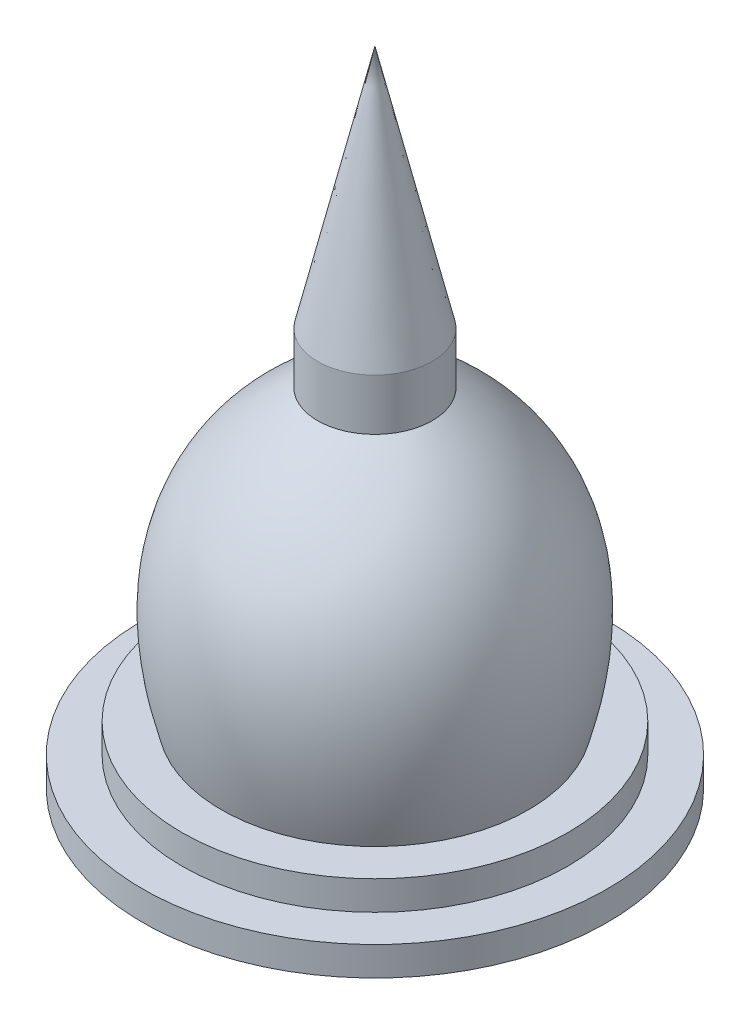
SolidWorks part; units mm, degrees
ref_plane "Front Plane" through (0, 0, 0) normal (0, 0, 1) x (1, 0, 0)
ref_plane "Top Plane" through (0, 0, 0) normal (0, 1, 0) x (1, 0, 0)
ref_plane "Right Plane" through (0, 0, 0) normal (1, 0, 0) x (0, 0, -1)
sketch "Sketch1" plane through (0, 0, 0) normal (0, 0, 1) x (1, 0, 0)
  line L0 (0, 0) -> (0, 120.0387) construction
  line L1 (0, 0) -> (-60, 0)
  line L2 (-60, 0) -> (-60, 7.5011)
  line L3 (-49.8183, 15.0034) -> (-39.6365, 15.0034)
  line L4 (-14.8078, 89.5954) -> (-14.8078, 102.8571)
  line L5 (-14.8078, 102.8571) -> (0, 165.9745)
  line L6 (-49.8183, 15.0034) -> (-49.8183, 7.5023)
  line L7 (-49.8183, 7.5023) -> (-60, 7.5011)
  line L9 (0, 0) -> (0, 165.9745)
  line L10 (0, 165.9745) -> (0, 0)
  line L12 (0, 120.0387) -> (0, 183.2545) construction
  spline S0 degree 2 poles (-39.6365, 15.0034) (-53.8427, 64.8006) (-14.8078, 89.5954) knots 0 0 0 1 1 1
  dimension "D1" = 60
revolve "Revolve1" add sketch "Sketch1" angle 360 about L9 region at (-18.9186, 51.2008, 0)
scale "Scale1" scale about centroid uniform scaling yes scale factor 3
